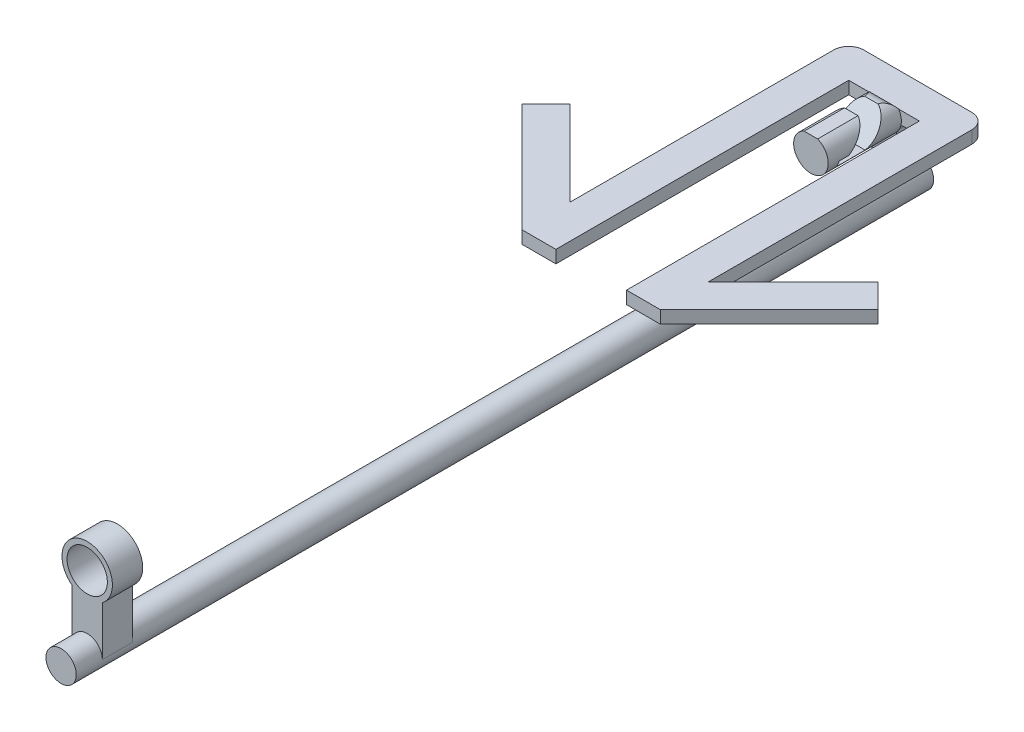
SolidWorks part; units mm, degrees
ref_plane "Front Plane" through (0, 0, 0) normal (0, 0, 1) x (1, 0, 0)
ref_plane "Top Plane" through (0, 0, 0) normal (0, 1, 0) x (1, 0, 0)
ref_plane "Right Plane" through (0, 0, 0) normal (1, 0, 0) x (0, 0, -1)
sketch "Sketch1" plane through (0, 0, 0) normal (0, 0, 1) x (1, 0, 0)
  circle A0 centre (0, 0) radius 3
  dimension "D1" = 6
extrude "Boss-Extrude1" add sketch "Sketch1" along normal blind 170
sketch "Sketch3" plane through (0, 0, 0) normal (0, 1, 0) x (1, 0, 0)
  line L1 (-2.4255, -0.1434) -> (2.4255, -0.1434)
  line L2 (-2.4255, -0.1434) -> (-2.4255, -6.8346)
  line L3 (-2.4255, -6.8346) -> (2.4255, -6.8346)
  line L4 (2.4255, -0.1434) -> (2.4255, -6.8346)
  line L5 (-2.4255, -0.1434) -> (2.4255, -6.8346) construction
  line L6 (-2.4255, -6.8346) -> (2.4255, -0.1434) construction
  point P0 (0, -3.489)
extrude "Boss-Extrude2" add sketch "Sketch3" along normal blind 13
sketch "Sketch5" plane through (0, 13, 0) normal (0, 1, 0) x (1, 0, 0)
  line L0 (-2.4255, -6.8346) -> (2.4255, -0.1434) construction
  line L1 (0, -6.8346) -> (0, -0.1434) construction
  line L2 (-7, -0.1434) -> (7, -0.1434)
  line L3 (-7, -0.1434) -> (-7, -6.8346)
  line L4 (-7, -6.8346) -> (7, -6.8346)
  line L5 (7, -0.1434) -> (7, -6.8346)
  line L6 (-7, -0.1434) -> (7, -6.8346) construction
  line L7 (-7, -6.8346) -> (7, -0.1434) construction
  line L8 (-7, -64.8964) -> (-13.7, -64.8964)
  line L9 (7, -0.1434) -> (13.7, -0.1434)
  line L10 (7, -0.1434) -> (7, -64.8964)
  line L11 (7, -64.8964) -> (13.7, -64.8964)
  line L12 (13.7, -0.1434) -> (13.7, -55.4212)
  line L13 (-13.7, -0.1434) -> (-13.7, -55.4212)
  line L14 (-7, -0.1434) -> (-13.7, -0.1434)
  line L15 (-7, -0.1434) -> (-7, -64.8964)
  line L16 (2.4255, -0.1434) -> (-2.4255, -0.1434) construction
  line L17 (13.7, -64.8964) -> (35.2687, -43.3278)
  line L18 (13.7, -55.4212) -> (30.531, -38.5902)
  line L19 (35.2687, -43.3278) -> (30.531, -38.5902)
  line L20 (-13.7, -64.8964) -> (-35.2687, -43.3278)
  line L21 (-35.2687, -43.3278) -> (-30.531, -38.5902)
  line L22 (-13.7, -55.4212) -> (-30.531, -38.5902)
  point P2 (0, -3.489)
  point P21 (30.5304, -38.5908)
  line M6 (2.4255, -6.8346) -> (2.4255, -0.1434)
  line M7 (2.4255, -0.1434) -> (-2.4255, -0.1434)
  line M8 (-2.4255, -0.1434) -> (-2.4255, -6.8346)
  line M9 (-2.4255, -6.8346) -> (2.4255, -6.8346)
  dimension "D1" = 6.7
  dimension "D2" = 45
  dimension "D3" = 14
  dimension "D4" = 64.753
  dimension "D5" = 6.7
extrude "Boss-Extrude4" add sketch "Sketch5" along normal blind 2.5 contours L12 L9 L5 L10 L11 | L15 L3 L14 L13 L8 | L3 L4 L2 M8 | M9 M6 M7 M8 | L5 L2 L4 M6 region at (-4.7127, 13, 3.489) region at (-7.7065, 13, 3.489) region at (0, 13, 3.489) region at (4.7127, 13, 3.489) region at (10.35, 13, 0.85)
fillet "Fillet1" radius 1.5 2 edges at (2.4255, 13, 3.489) (-2.4255, 13, 3.489)
fillet "Fillet2" radius 3 2 edges at (-13.7, 14.25, 0.1434) (13.7, 14.25, 0.1434)
sketch "Sketch8" plane through (0, 0, 6.8346) normal (0, 0, 1) x (1, 0, 0)
  line L0 (-1.3412, 16.8431) -> (1.3412, 16.8431)
  arc A0 (-1.3412, 16.8431) -> (1.3412, 16.8431) centre (0, 13.6885) ccw
extrude "Boss-Extrude6" add sketch "Sketch8" along normal blind 14.5
fillet "Fillet3" radius 3 1 edges at (0, 16.8431, 6.8346)
sketch "Sketch14" plane through (0, 0, 0) normal (1, 0, 0) x (0, 0, -1)
  line L0 (-9.3355, 16.8431) -> (-13.3355, 16.8431)
  line L1 (-21.3346, 16.8431) -> (-9.3355, 16.8431) construction
  line L2 (-13.3355, 16.8431) -> (-17.1614, 12.9181)
  line L3 (-18.4197, 11.6272) -> (-13.3355, 11.6272)
  line L4 (-13.3355, 11.6272) -> (-9.3355, 16.8431)
  line L6 (-13.3355, 11.6272) -> (-19.0743, 11.6272)
  line L8 (-17.1614, 12.9181) -> (-19.0743, 12.9181)
  line L9 (-19.0743, 11.6272) -> (-19.0743, 12.9181)
  dimension "D1" = 4
  dimension "D2" = 3.8259
  dimension "D3" = 1.9128
extrude "Cut-Extrude1" cut sketch "Sketch14" against normal blind 4.5 and the other way blind 4 contours L4 L0 L2 L8 L9 L6
sketch "Sketch15" plane through (0, 0, 0) normal (0, 1, 0) x (1, 0, 0)
  line L0 (3, -170) -> (3, 0) construction
  line L1 (3, -164.8235) -> (-3, -164.8235)
  line L2 (3, -164.8235) -> (3, -158.825)
  line L3 (3, -158.825) -> (-3, -158.825)
  line L4 (-3, -164.8235) -> (-3, -158.825)
  line L5 (-3, 0) -> (-3, -170) construction
extrude "Boss-Extrude7" add sketch "Sketch15" along normal up to surface (16.8431 mm away) up to face at (0, 16.8431, 17.335)
sketch "Sketch16" plane through (0, 0, 158.825) normal (0, 0, -1) x (-1, 0, 0)
  circle A0 centre (0, 13.8034) radius 4
  circle A1 centre (0, 13.8034) radius 5
  point P2 (0, 13.8319)
  point P4 (0, 13.8034)
  dimension "D1" = 8
  dimension "D2" = 10
extrude "Boss-Extrude9" add sketch "Sketch16" against normal up to surface (5.9985 mm away) up to face at (0, 9.1716, 164.8235)
sketch "Sketch17" plane through (0, 0, 164.8235) normal (0, 0, 1) x (1, 0, 0)
  circle A0 centre (0, 13.8034) radius 4
  arc A1 (3, 11.1576) -> (3, 16.4491) centre (0, 13.8034) ccw construction
extrude "Cut-Extrude6" cut sketch "Sketch17" against normal up to surface (5.9985 mm away) up to face at (-3.5, 13.8034, 158.825)
